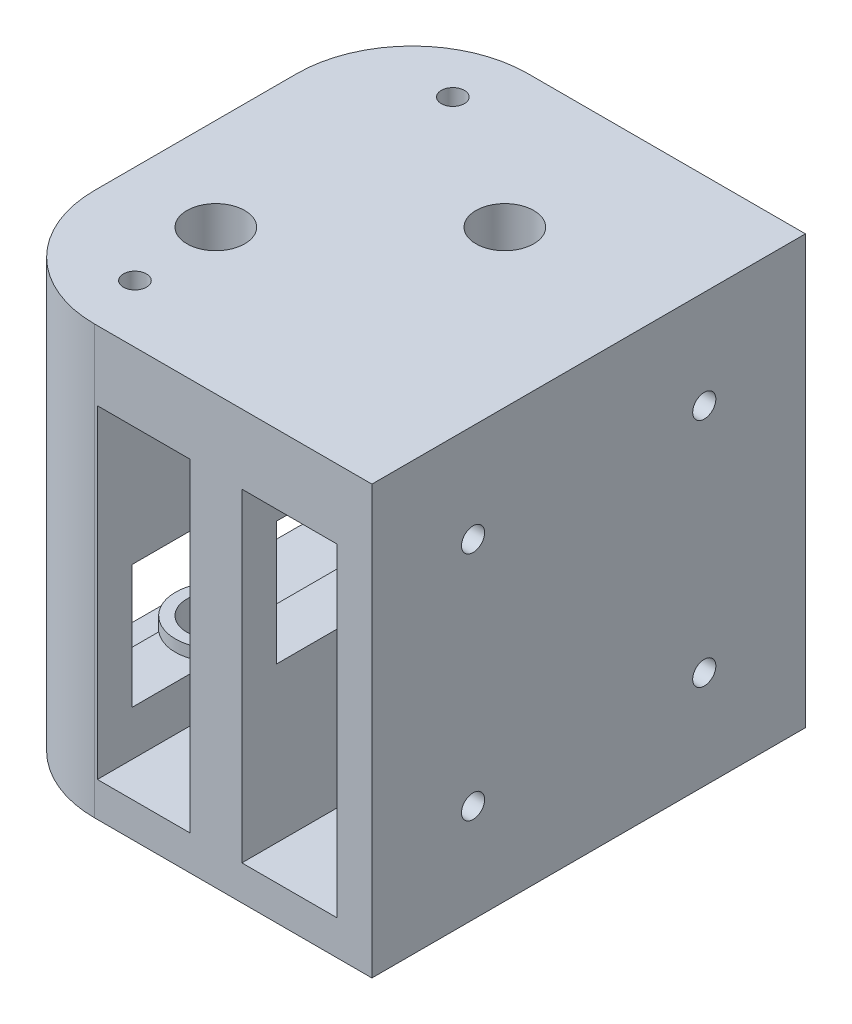
SolidWorks part; units mm, degrees
ref_plane "Front Plane" through (0, 0, 0) normal (0, 0, 1) x (1, 0, 0)
ref_plane "Top Plane" through (0, 0, 0) normal (0, 1, 0) x (1, 0, 0)
ref_plane "Right Plane" through (0, 0, 0) normal (1, 0, 0) x (0, 0, -1)
sketch "Top-Sketch1" plane through (0, 0, 0) normal (0, 1, 0) x (1, 0, 0)
  line L1 (0, 0) -> (34, 0)
  line L2 (0, 0) -> (0, 37.5)
  line L3 (0, 37.5) -> (34, 37.5)
  line L4 (34, 0) -> (34, 37.5)
  circle A0 centre (8.5, 32.5) radius 1
  circle A1 centre (8.5, 5) radius 1
  circle A2 centre (8, 12.5) radius 2.5
  circle A3 centre (20.5, 25) radius 2.5
  dimension "D3" = 5
  dimension "D5" = 2
  dimension "D1" = 13.5
  dimension "D2" = 12.5
  dimension "D4" = 12.5
  dimension "D6" = 8
  dimension "D8" = 12.5
  dimension "D9" = 5
  dimension "D10" = 5
  dimension "D11" = 37.5
  dimension "D12" = 12.5
  dimension "D7" = 25.5
extrude "Boss-Extrude4" add sketch "Top-Sketch1" along normal blind 6
sketch "TopRightRiser" plane through (0, 0, 0) normal (0, -1, 0) x (1, 0, 0)
  line L0 (5.75, -9.819) -> (5.75, 0)
  line L1 (0, 0) -> (34, 0) construction
  line L2 (5.75, 0) -> (10.25, 0)
  line L3 (10.25, 0) -> (10.25, -9.819)
  arc A0 (5.75, -9.819) -> (10.25, -9.819) centre (8, -12.5) ccw
  circle A1 centre (8, -12.5) radius 2.5 construction
  circle A2 centre (8, -12.5) radius 2.5
  point P13 (8, 0)
  dimension "D1" = 7
  dimension "D2" = 4.5
extrude "TopRightRiserBoss-Extrude5" add sketch "TopRightRiser" along normal blind 14.4
sketch "TopLeft" plane through (0, 0, 0) normal (0, -1, 0) x (1, 0, 0)
  line L0 (18.25, -22.319) -> (18.25, 0)
  line L1 (10.25, 0) -> (34, 0) construction
  line L2 (18.25, 0) -> (22.75, 0)
  line L3 (22.75, 0) -> (22.75, -22.319)
  line L4 (10.25, 0) -> (5.75, 0) construction
  circle A0 centre (20.5, -25) radius 2.5
  circle A1 centre (20.5, -25) radius 2.5 construction
  arc A2 (18.25, -22.319) -> (22.75, -22.319) centre (20.5, -25) ccw
  arc A3 (5.75, -9.819) -> (10.25, -9.819) centre (8, -12.5) ccw construction
  point P16 (20.5, 0)
extrude "TopLeftBoss-Extrude6" add sketch "TopLeft" along normal blind 4.9
sketch "MidWall" plane through (0, 0, 0) normal (0, -1, 0) x (-1, 0, 0)
  line L0 (-10.25, 9.819) -> (-10.25, 0) construction
  line L1 (0, 3) -> (-10.25, 3)
  line L2 (0, 3) -> (0, 0)
  line L3 (0, 0) -> (-10.25, 0)
  line L4 (-10.25, 3) -> (-10.25, 0)
  line L5 (0, 37.5) -> (0, 0) construction
  line L6 (-10.25, 0) -> (-5.75, 0) construction
  line L7 (-18.25, 0) -> (-18.25, 22.319) construction
  line L8 (-18.25, 0) -> (-22.75, 0)
  line L9 (-18.25, 0) -> (-18.25, 3)
  line L10 (-18.25, 3) -> (-22.75, 3)
  line L11 (-22.75, 0) -> (-22.75, 3)
  line L12 (-22.75, 22.319) -> (-22.75, 0) construction
  line L13 (-10.25, 0) -> (-18.25, 0) construction
  line L14 (-22.75, 0) -> (-34, 0) construction
  line L15 (-31, 0) -> (-34, 0)
  line L16 (-31, 0) -> (-31, 37.5)
  line L17 (-31, 37.5) -> (-34, 37.5)
  line L18 (-34, 0) -> (-34, 37.5)
  line L19 (-34, 37.5) -> (0, 37.5) construction
  line L20 (-34, 0) -> (-34, 37.5) construction
  dimension "D1" = 3
extrude "MidWallBoss-Extrude7" add sketch "MidWall" along normal blind 28
sketch "Bottom" plane through (0, -28, 0) normal (0, -1, 0) x (1, 0, 0)
  line L0 (0, 0) -> (34, 0) construction
  line L1 (0, 0) -> (34, 0)
  line L2 (0, 0) -> (0, -37.5)
  line L3 (0, -37.5) -> (34, -37.5)
  line L4 (34, 0) -> (34, -37.5)
  line L5 (34, 0) -> (34, -37.5) construction
  line L6 (0, -37.5) -> (0, 0) construction
extrude "BottomBoss-Extrude8" add sketch "Bottom" along normal blind 3
sketch "LowerRight" plane through (0, -28, 0) normal (0, 1, 0) x (1, 0, 0)
  line L0 (5.75, 9.819) -> (5.75, 3)
  line L1 (5.75, 3) -> (10.25, 3)
  line L2 (10.25, 3) -> (10.25, 9.819)
  line L6 (10.25, 9.819) -> (10.25, 3) construction
  line L7 (5.75, 3) -> (5.75, 9.819) construction
  line L8 (10.25, 3) -> (5.75, 3) construction
  circle A0 centre (8, 12.5) radius 2.5
  arc A1 (10.25, 9.819) -> (5.75, 9.819) centre (8, 12.5) ccw
  circle A2 centre (8, 12.5) radius 2.5 construction
  arc A3 (10.25, 9.819) -> (5.75, 9.819) centre (8, 12.5) ccw construction
extrude "LowerRightBoss-Extrude10" add sketch "LowerRight" along normal blind 4.9
sketch "LowerLeft" plane through (0, -28, 0) normal (0, 1, 0) x (1, 0, 0)
  line L1 (18.25, 0) -> (22.75, 0)
  line L5 (0, 0) -> (34, 0) construction
  line L6 (18.25, 22.319) -> (18.25, 0)
  line L7 (22.75, 22.319) -> (22.75, 0)
  circle A0 centre (20.5, 25) radius 2.5
  arc A1 (22.75, 22.319) -> (18.25, 22.319) centre (20.5, 25) ccw
  circle A2 centre (20.5, 25) radius 2.5 construction
  arc A3 (22.75, 22.319) -> (18.25, 22.319) centre (20.5, 25) ccw construction
  point P3 (20.5, 0)
  dimension "D1" = 4.5
extrude "LowerLeftBoss-Extrude9" add sketch "LowerLeft" along normal blind 14.4
fillet "Fillet1" radius 10 3 edges at (0, -12.5, 0) (0, -29.5, -37.5) (0, 3, -37.5)
sketch "LinearRailMountingHoles-Sketch10" plane through (34, 0, 0) normal (1, 0, 0) x (0, 0, -1)
  line L0 (0, 6) -> (37.5, 6) construction
  line L1 (37.5, 6) -> (37.5, -31) construction
  line L3 (37.5, -31) -> (0, -31) construction
  line L4 (0, 6) -> (0, -31) construction
  circle A0 centre (8.75, -2.5) radius 1
  circle A1 centre (8.75, -22.5) radius 1
  circle A2 centre (28.75, -22.5) radius 1
  circle A3 centre (28.75, -2.5) radius 1
  dimension "D7" = 2
  dimension "D1" = 8.5
  dimension "D2" = 20
  dimension "D3" = 20
  dimension "D4" = 8.75
  dimension "D5" = 8.5
  dimension "D6" = 8.75
extrude "LinearRailMountingHolesCut-Extrude1" cut sketch "LinearRailMountingHoles-Sketch10" against normal blind 3
sketch "TopRightInset-Sketch1" plane through (0, -14.4, 0) normal (0, -1, 0) x (1, 0, 0)
  line L0 (5.75, -9.819) -> (5.75, -3)
  line L1 (5.75, -3) -> (10.25, -3)
  line L2 (10.25, -3) -> (10.25, -9.819)
  line L3 (5.75, -9.819) -> (5.75, -3) construction
  line L4 (5.75, -3) -> (10.25, -3) construction
  line L5 (10.25, -3) -> (10.25, -9.819) construction
  arc A0 (10.25, -9.819) -> (5.75, -9.819) centre (8, -12.5) ccw
  arc A1 (5.75, -9.819) -> (10.25, -9.819) centre (8, -12.5) ccw construction
extrude "TopRightInset-Cut-Extrude1" cut sketch "TopRightInset-Sketch1" against normal blind 1
sketch "TopLeftInset-Sketch2" plane through (0, -4.9, 0) normal (0, -1, 0) x (1, 0, 0)
  line L0 (18.25, -22.319) -> (18.25, -3)
  line L1 (18.25, -3) -> (22.75, -3)
  line L2 (22.75, -3) -> (22.75, -22.319)
  line L3 (22.75, -3) -> (18.25, -3) construction
  line L4 (22.75, -22.319) -> (22.75, -3) construction
  line L5 (18.25, -22.319) -> (18.25, -3) construction
  arc A0 (22.75, -22.319) -> (18.25, -22.319) centre (20.5, -25) ccw
  arc A1 (18.25, -22.319) -> (22.75, -22.319) centre (20.5, -25) ccw construction
extrude "TopLeftInset-Cut-Extrude2" cut sketch "TopLeftInset-Sketch2" against normal blind 1
sketch "LowerLeftInset-Sketch3" plane through (0, -13.6, 0) normal (0, 1, 0) x (1, 0, 0)
  line L0 (18.25, 22.319) -> (18.25, 3)
  line L1 (18.25, 3) -> (22.75, 3)
  line L2 (22.75, 3) -> (22.75, 22.319)
  line L3 (22.75, 3) -> (18.25, 3) construction
  line L4 (18.25, 22.319) -> (18.25, 3) construction
  line L5 (22.75, 3) -> (22.75, 22.319) construction
  arc A0 (18.25, 22.319) -> (22.75, 22.319) centre (20.5, 25) ccw
  arc A1 (22.75, 22.319) -> (18.25, 22.319) centre (20.5, 25) ccw construction
extrude "LowerLeftInset-Cut-Extrude3" cut sketch "LowerLeftInset-Sketch3" against normal blind 1
sketch "LowerRightInset-Sketch4" plane through (0, -23.1, 0) normal (0, 1, 0) x (1, 0, 0)
  line L0 (5.75, 9.819) -> (5.75, 3)
  line L1 (5.75, 3) -> (10.25, 3)
  line L2 (10.25, 3) -> (10.25, 9.819)
  line L3 (10.25, 3) -> (5.75, 3) construction
  line L4 (5.75, 3) -> (5.75, 9.819) construction
  line L5 (10.25, 9.819) -> (10.25, 3) construction
  arc A0 (5.75, 9.819) -> (10.25, 9.819) centre (8, 12.5) ccw
  arc A1 (10.25, 9.819) -> (5.75, 9.819) centre (8, 12.5) ccw construction
extrude "LowerRightInsetCut-Extrude4" cut sketch "LowerRightInset-Sketch4" against normal blind 1
sketch "PushPinHoleSketch1" plane through (0, -31, 0) normal (0, -1, 0) x (1, 0, 0)
  circle A0 centre (20.5, -25) radius 1
  circle A1 centre (8, -12.5) radius 1
  circle A2 centre (8, -12.5) radius 2.5 construction
  circle A3 centre (20.5, -25) radius 2.5 construction
  point P8 (0, 0)
  dimension "D1" = 2
extrude "PushPinHoleCut-Extrude5" cut sketch "PushPinHoleSketch1" against normal through all
equation "\"GABDepth\"= \"GABDistanceFromBackToFirstPulley\" + \"GABPulleyDDistanceBetween\" + \"GABDistanceFromPulleyToFront\""
equation "\"GABWidth\"= \"StandardWallThickness\" + \"GABDistanceFromLSideToPulley\" + \"GABPulleyWDistanceBetween\" + \"GABDistanceFromPulleyToRSide\""
equation "\"GABLowerHeight\"= 3mm"
equation "\"GABUpperHeight\"= 6mm"
equation "\"GABMidWallHeight\"= 28mm'Must equal 28 or changes alignment"
equation "\"StandardWallThickness\"= 3mm"
equation "\"GABMidShortRiserHeight\"= \"GABMidWallHeight\" / 2 - \"20TGT2PulleyWidth\"'Equals 5.3"
equation "\"LinearGBMountHolesXDistance\"= 20mm'Spec"
equation "\"GABHeight\"= \"GABLowerHeight\" + \"GABMidWallHeight\" + \"GABUpperHeight\""
equation "\"GBMountingHoleDiameter\"= 2mm"
equation "\"GABMidLongRiserHeight\"= \"GABMidWallHeight\" - \"GABMidShortRiserHeight\" - \"20TGT2PulleyWidth\"'Equals 14"
equation "\"GABLRClampHoleOffsetFromSide\"= 5mm"
equation "\"GABDistanceFromBackToFirstPulley\"= 13.5mm"
equation "\"GABPulleyDDistanceBetween\"= 12.5mm'From the100"
equation "\"GABPulleyWDistanceBetween\"= 14.5mm'From the100"
equation "\"GABDistanceFromPulleyToFront\"= 8mm"
equation "\"GABDistanceFromLSideToPulley\"= 9.5mm + \"StandardWallThickness\""
equation "\"GABDistanceFromPulleyToRSide\"= 7.5mm"
equation "\"GABDistanceToFrontClampHoles\"= 8.5mm"
equation "\"SteelShaft5mmHoleDiameter\"= 5mm"
equation "\"20TGT2PulleyWidth\"= 8.7mm'The STL of the Pulley in the diagram is a bit larger"
equation "\"7mmx1mmSpacerDiameter\"= 7mm"
equation "\"7mmx1mmSpacerHeight\"= 1mm"
equation "\"GABRiserBossOffset\"= 0.8mm'Aligns Pulleys"
equation "\"D1@Top-Sketch1\" = \"GABDistanceFromBackToFirstPulley\""
equation "\"D2@Top-Sketch1\" = \"GABPulleyDDistanceBetween\""
equation "\"D3@Top-Sketch1\" = \"SteelShaft5mmHoleDiameter\""
equation "\"D4@Top-Sketch1\" = \"GABPulleyDDistanceBetween\""
equation "\"D6@Top-Sketch1\" = \"GABDistanceFromPulleyToFront\""
equation "\"D8@Top-Sketch1\" = \"GABDistanceFromLSideToPulley\""
equation "\"D9@Top-Sketch1\" = \"GABLRClampHoleOffsetFromSide\""
equation "\"D10@Top-Sketch1\" = \"GABLRClampHoleOffsetFromSide\""
equation "\"D11@Top-Sketch1\" = \"GABWidth\""
equation "\"D1@Boss-Extrude4\"=\"GABUpperHeight\""
equation "\"D1@TopRightRiserBoss-Extrude5\" = \"GABMidLongRiserHeight\" + \"GABRiserBossOffset\" / 2"
equation "\"D1@TopLeftBoss-Extrude6\" = \"GABMidShortRiserHeight\" - \"GABRiserBossOffset\" / 2"
equation "\"D1@MidWall\" = \"StandardWallThickness\""
equation "\"D1@MidWallBoss-Extrude7\" = \"GABMidWallHeight\""
equation "\"D1@BottomBoss-Extrude8\" = \"GABLowerHeight\""
equation "\"D1@LowerLeftBoss-Extrude9\"=\"GABMidLongRiserHeight\" + \"GABRiserBossOffset\"/2"
equation "\"D1@LowerRightBoss-Extrude10\"=\"GABMidShortRiserHeight\" - \"GABRiserBossOffset\" / 2"
equation "\"D1@LinearRailMountingHoles-Sketch10\" =  ( \"GABHeight\" - \"LinearGBMountHolesXDistance\" )  / 2"
equation "\"D2@LinearRailMountingHoles-Sketch10\"=\"LinearGBMountHolesYDistance\""
equation "\"D3@LinearRailMountingHoles-Sketch10\" = \"LinearGBMountHolesXDistance\""
equation "\"D4@LinearRailMountingHoles-Sketch10\" =  ( \"GABWidth\" - \"LinearGBMountHolesXDistance\" )  / 2"
equation "\"D7@LinearRailMountingHoles-Sketch10\" = \"GBMountingHoleDiameter\""
equation "\"D1@LinearRailMountingHolesCut-Extrude1\" = \"StandardWallThickness\""
equation "\"D1@TopRightInset-Cut-Extrude1\" = \"7mmx1mmSpacerHeight\""
equation "\"D1@TopLeftInset-Cut-Extrude2\" = \"7mmx1mmSpacerHeight\""
equation "\"D1@LowerRightInsetCut-Extrude4\" = \"7mmx1mmSpacerHeight\""
equation "\"D1@TopRightRiser\"=\"7mmx1mmSpacerDiameter\""
equation "\"D7@Top-Sketch1\"=\"GABDepth\" - \"GABDistanceToFrontClampHoles\""
equation "\"LinearGBMountHolesYDistance\"= 20mm'Spec"
equation "\"D1@PushPinHoleSketch1\" = \"StealPinPushHoleDiameter\""
equation "\"StealPinPushHoleDiameter\"= 2mm"
